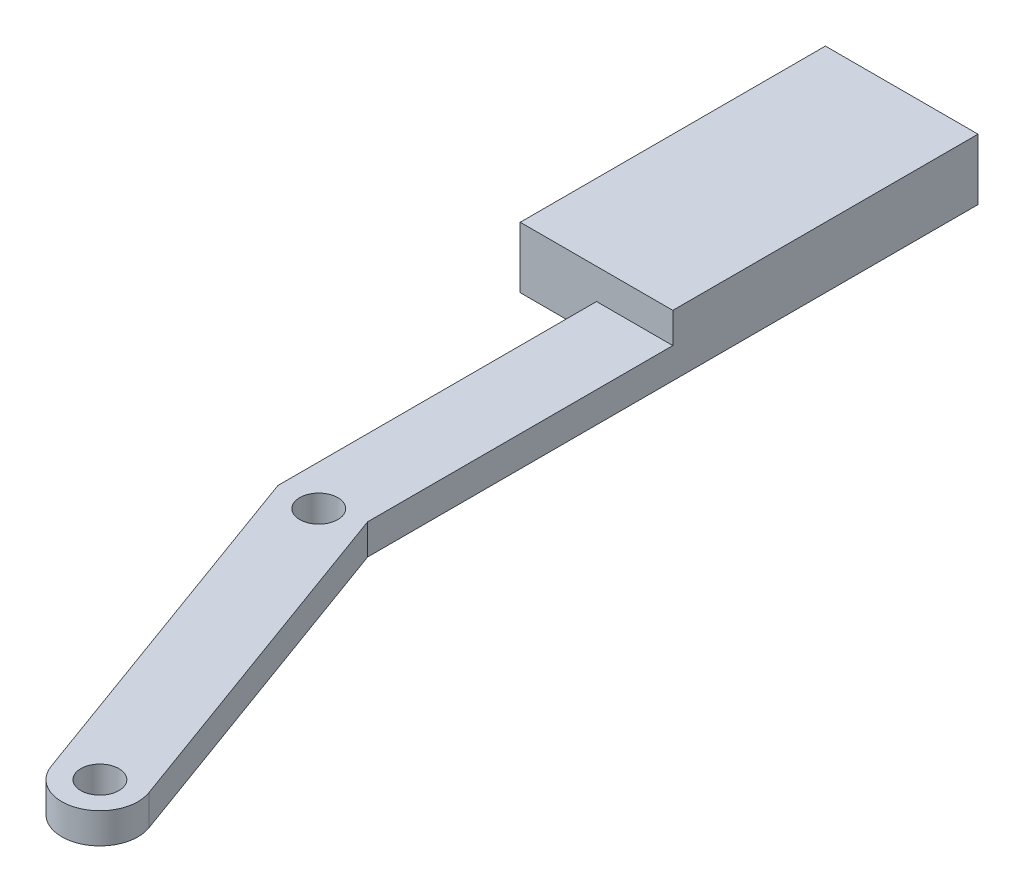
SolidWorks part; units mm, degrees
material "AISI 316 Stainless Steel Sheet (SS)"
ref_plane "Front Plane" through (0, 0, 0) normal (0, 0, 1) x (1, 0, 0)
ref_plane "Top Plane" through (0, 0, 0) normal (0, 1, 0) x (1, 0, 0)
ref_plane "Right Plane" through (0, 0, 0) normal (1, 0, 0) x (0, 0, -1)
sketch "Sketch1" plane through (0, 0, 0) normal (0, 1, 0) x (1, 0, 0)
  line L0 (-6.35, -13.8197) -> (-6.35, 12.7)
  line L1 (0, -12.7) -> (0, 38.1)
  line L2 (0, 38.1) -> (-12.7, 38.1)
  line L3 (-12.7, 38.1) -> (-12.7, 12.7)
  line L4 (-12.7, 12.7) -> (-6.35, 12.7)
  line L5 (0, -12.7) -> (10.4248, -41.3418)
  line L6 (-6.35, -13.8197) -> (4.4577, -43.5137)
  line L7 (0, -12.7) -> (-5.967, -14.8718) construction
  arc A0 (4.4577, -43.5137) -> (10.4248, -41.3418) centre (7.4412, -42.4277) ccw
  circle A1 centre (7.4412, -42.4277) radius 1.5875
  circle A2 centre (-2.9835, -13.7859) radius 1.5875
  dimension "D1" = 3.175
  dimension "D2" = 3.175
  dimension "D6" = 3.175
  dimension "D3" = 160
  dimension "D4" = 6.35
  dimension "D8" = 30.48
  dimension "D10" = 12.7
  dimension "D11" = 50.8
  dimension "D12" = 25.4
  dimension "D13" = 12.7
extrude "Boss-Extrude1" add sketch "Sketch1" along normal blind 5.08
sketch "Sketch2" plane through (0, 5.08, 0) normal (0, 1, 0) x (1, 0, 0)
  line L1 (-6.35, -13.8197) -> (5.5436, -46.4972)
  line L2 (0, -12.7) -> (11.5107, -44.3254)
  line L3 (11.5107, -44.3254) -> (5.5436, -46.4972)
  line L4 (-6.35, -13.8197) -> (4.4577, -43.5137) construction
  line L5 (10.4248, -41.3418) -> (0, -12.7) construction
  line L6 (-6.35, 12.7) -> (0, 12.7)
  line L7 (0, -12.7) -> (0, 38.1) construction
  line L8 (0, 12.7) -> (0, -12.7)
  line L9 (-6.35, -13.8197) -> (-6.35, 12.7)
  arc A0 (4.4577, -43.5137) -> (10.4248, -41.3418) centre (7.4412, -42.4277) ccw construction
extrude "Right Cut" cut sketch "Sketch2" against normal blind 2.54
sketch "Sketch3" plane through (0, 5.08, 0) normal (0, 1, 0) x (1, 0, 0)
  line L0 (-12.7, 38.1) -> (-13.97, 36.83)
  line L1 (-13.97, 36.83) -> (-12.7, 35.56)
  line L2 (-12.7, 38.1) -> (-12.7, 12.7) construction
  line L12 (-12.7, 38.1) -> (0, 38.1)
  line L13 (0, 38.1) -> (0, 12.7)
  line L14 (0, 12.7) -> (0, 38.1) construction
  line L16 (-13.97, 34.29) -> (-12.7, 33.02)
  line L17 (-12.7, 35.56) -> (-13.97, 34.29)
  line L18 (-13.97, 31.75) -> (-12.7, 30.48)
  line L19 (-12.7, 33.02) -> (-13.97, 31.75)
  line L20 (-13.97, 29.21) -> (-12.7, 27.94)
  line L21 (-12.7, 30.48) -> (-13.97, 29.21)
  line L22 (-13.97, 26.67) -> (-12.7, 25.4)
  line L23 (-12.7, 27.94) -> (-13.97, 26.67)
  line L24 (-13.97, 24.13) -> (-12.7, 22.86)
  line L25 (-12.7, 25.4) -> (-13.97, 24.13)
  line L26 (-13.97, 21.59) -> (-12.7, 20.32)
  line L27 (-12.7, 22.86) -> (-13.97, 21.59)
  line L28 (-13.97, 19.05) -> (-12.7, 17.78)
  line L29 (-12.7, 20.32) -> (-13.97, 19.05)
  line L30 (-13.97, 16.51) -> (-12.7, 15.24)
  line L31 (-12.7, 17.78) -> (-13.97, 16.51)
  line L32 (-13.97, 13.97) -> (-12.7, 12.7)
  line L33 (-12.7, 15.24) -> (-13.97, 13.97)
  line L34 (-12.7, 12.7) -> (0, 12.7)
  dimension "D1" = 2.54
  dimension "D2" = 135
  dimension "D3" = 10
extrude "Boss-Extrude2" [suppressed] add sketch "Sketch3" against normal up to surface (5.08 mm away) contours L13 L34 L32 L33 L30 L31 L28 L29 L26 L27 L24 L25 L22 L23 L20 L21 L18 L19 L16 L17 L1 L0 L12 up to face at (-2.7664, 0, 1.5948)
sketch "Sketch4" plane through (0, 0, 0) normal (0, -1, 0) x (1, 0, 0)
  line L0 (-6.35, -12.7) -> (-6.35, 13.8197)
  line L1 (-6.35, 13.8197) -> (4.4577, 43.5137) construction
  line L2 (-6.35, -12.7) -> (-6.35, 13.8197) construction
  line L3 (-6.35, 13.8197) -> (5.5436, 46.4972)
  line L4 (5.5436, 46.4972) -> (11.5107, 44.3254)
  line L5 (-6.35, -12.7) -> (0, -12.7)
  line L7 (0, -12.7) -> (0, 12.7)
  line L8 (0, 12.7) -> (11.5107, 44.3254)
  line L9 (10.4248, 41.3418) -> (0, 12.7) construction
  arc A0 (10.4248, 41.3418) -> (4.4577, 43.5137) centre (7.4412, 42.4277) ccw construction
extrude "Left Cut" [suppressed] cut sketch "Sketch4" against normal blind 2.54
